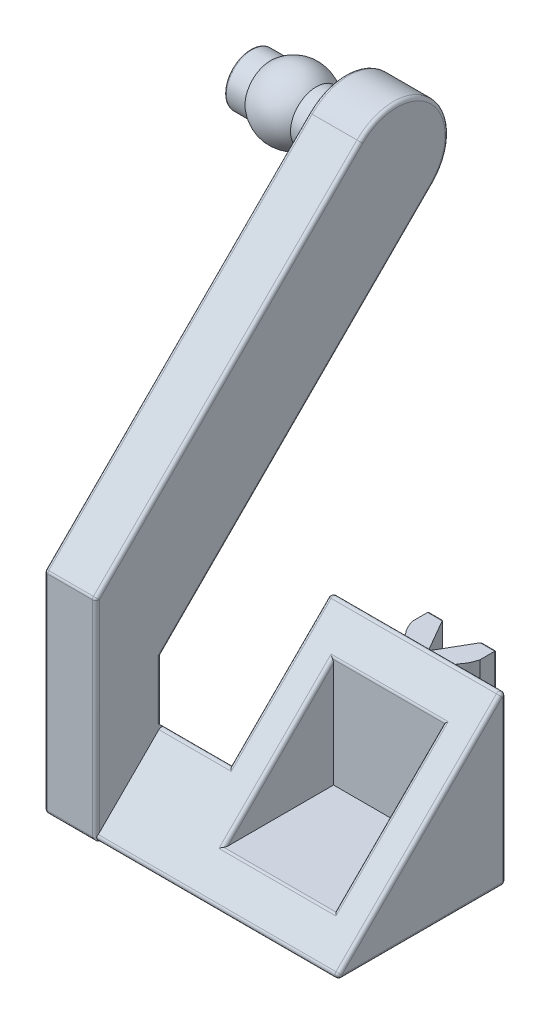
SolidWorks part; units mm, degrees
ref_plane "前视基准面" through (0, 0, 0) normal (0, 0, 1) x (1, 0, 0)
ref_plane "上视基准面" through (0, 0, 0) normal (0, 1, 0) x (1, 0, 0)
ref_plane "右视基准面" through (0, 0, 0) normal (1, 0, 0) x (0, 0, -1)
sketch "草图1" plane through (0, 0, 0) normal (1, 0, 0) x (0, 0, -1)
  line L0 (0, 0) -> (-10, 0)
  line L1 (-10, 0) -> (0, 10)
  line L2 (0, 10) -> (0, 0)
  dimension "D1" = 10
  dimension "D2" = 10
extrude "凸台-拉伸1" add sketch "草图1" along normal blind 10
sketch "草图2" plane through (0, 0, 0) normal (0, 0, 1) x (1, 0, 0)
  line L0 (0, 10) -> (0, 0) construction
  line L1 (1.8, 1.8) -> (8.2, 1.8)
  line L2 (1.8, 1.8) -> (1.8, 8.2)
  line L3 (1.8, 8.2) -> (8.2, 8.2)
  line L4 (8.2, 1.8) -> (8.2, 8.2)
  line L5 (10, 10) -> (10, 0) construction
  line L6 (10, 0) -> (0, 0) construction
  line L7 (10, 10) -> (0, 10) construction
  dimension "D1" = 1.8
  dimension "D2" = 1.8
  dimension "D3" = 1.8
  dimension "D4" = 1.8
extrude "切除-拉伸1" cut sketch "草图2" along normal up to next from offset 1.8
sketch "草图3" plane through (0, 0, 0) normal (-1, 0, 0) x (0, 0, 1)
  line L0 (10, 0) -> (2, 0)
  line L1 (10, 0) -> (0, 0) construction
  line L2 (2, 0) -> (6, 4)
  line L3 (0, 10) -> (10, 0) construction
  line L4 (6, 4) -> (10, 0)
  dimension "D1" = 90
  dimension "D2" = 8
extrude "凸台-拉伸2" add sketch "草图3" along normal blind 4
sketch "草图4" plane through (-4, 0, 0) normal (-1, 0, 0) x (0, 0, 1)
  line L0 (10, 0) -> (10, 12) construction
  line L1 (6, 4) -> (6, 7.5147)
  line L2 (9.8, 12.2) -> (-5.5563, 27.5563)
  line L3 (10, 0) -> (6, 4)
  line L4 (6, 4) -> (2, 0)
  line L5 (2, 0) -> (10, 0)
  line L6 (6, 7.5147) -> (-9.799, 23.3137)
  line L7 (6, 4) -> (2, 0)
  line L8 (2, 0) -> (9.8, 0)
  line L9 (5.7574, 7.7574) -> (-9.799, 23.3137) construction
  line L10 (9.8, 0) -> (9.8, 12.2)
  line L11 (9.8, 0) -> (9.8, 12) construction
  line L12 (9.8, 12.2) -> (10, 12) construction
  line L13 (10, 12) -> (-5.5563, 27.5563) construction
  line L14 (9.8, 0) -> (10, 0) construction
  arc A0 (-5.5563, 27.5563) -> (-9.799, 23.3137) centre (-7.6777, 25.435) ccw
  dimension "D6" = 6
  dimension "D2" = 12
  dimension "D3" = 22
  dimension "D4" = 135
  dimension "D1" = 0
  dimension "D5" = 6
  dimension "D7" = 0.2
extrude "凸台-拉伸3" add sketch "草图4" along normal blind 3
sketch "草图5" plane through (-7, 0, 0) normal (-1, 0, 0) x (0, 0, 1)
  circle A0 centre (-7.6777, 25.435) radius 1.5
  dimension "D1" = 3
extrude "凸台-拉伸4" add sketch "草图5" along normal blind 5.5
ref_plane "基准面1" through (-10, 0, 0) normal (-1, 0, 0) x (0, 0, 1)
sketch "草图6" plane through (-10, 0, 0) normal (-1, 0, 0) x (0, 0, 1)
  line L0 (-7.6777, 27.435) -> (-7.6777, 23.435)
  arc A0 (-7.6777, 23.435) -> (-7.6777, 27.435) centre (-7.6777, 25.435) ccw
  dimension "D1" = 4
revolve "旋转1" add sketch "草图6" angle 360 about L0
sketch "草图7" plane through (0, 0, 0) normal (0, -1, 0) x (1, 0, 0)
  line L0 (5, 0) -> (5, -2) construction
  line L1 (10, 0) -> (0, 0) construction
  line L2 (5, -2) -> (5, -2.5) construction
  line L3 (6.5, 0) -> (3.5, 0)
  line L4 (3.5, 0) -> (3.5, -0.6771)
  line L5 (3.8453, -2.5) -> (3.05, -2.5)
  line L6 (3.05, -2.5) -> (3.05, -1.5556)
  line L7 (5, 0) -> (5, -0.5) construction
  line L8 (5, -0.5) -> (3.8453, -2.5)
  line L9 (3.8453, -2.5) -> (5, -2.5) construction
  line L10 (5, -0.5) -> (6.1547, -2.5)
  line L11 (6.1547, -2.5) -> (6.95, -2.5)
  line L12 (6.95, -2.5) -> (6.95, -1.5556)
  line L13 (6.5, 0) -> (6.5, -0.6771)
  arc A0 (3.5, -0.6771) -> (3.05, -1.5556) centre (5, -2) ccw
  arc A1 (6.5, -0.6771) -> (6.95, -1.5556) centre (5, -2) cw
  dimension "D5" = 2
  dimension "D1" = 2
  dimension "D2" = 0.5
  dimension "D3" = 1.5
  dimension "D4" = 1.95
  dimension "D6" = 0.5
  dimension "D7" = 30
extrude "凸台-拉伸5" add sketch "草图7" against normal blind 8 from offset 1 offset against normal yes
sketch "草图8" plane through (0, 0, 0) normal (0, -1, 0) x (1, 0, 0)
  line L0 (5, -0.5) -> (3.8453, -2.5)
  line L1 (3.8453, -2.5) -> (6.1547, -2.5)
  line L2 (6.1547, -2.5) -> (5, -0.5)
extrude "凸台-拉伸6" add sketch "草图8" against normal blind 1 from offset 4.5 offset against normal yes
fillet "圆角1" radius 0.1 12 edges at (6.95, 5, -2.5) (6.5524, 9, -2.5) (6.1547, 7.25, -2.5) (5, 5.5, -2.5) (3.8453, 7.25, -2.5) (3.4476, 9, -2.5) (3.05, 5, -2.5) (3.4476, 1, -2.5) (3.8453, 2.75, -2.5) (5, 4.5, -2.5) (6.1547, 2.75, -2.5) (6.5524, 1, -2.5)
fillet "圆角3" radius 0.2 15 edges at (10, 0, 5) (10, 5, 5) (10, 5, 0) (5, 8.2, 1.8) (8.2, 5, 5) (5, 1.8, 8.2) (1.8, 5, 5) (-7, 0, 5.9) (-7, 2, 4) (0, 5, 0) (5, 0, 0)
fillet "圆角7" radius 0.2 2 edges at (9.9414, 0.0586, 9.8586) (2.9, 0, 10)
fillet "圆角8" radius 0.2 12 edges at (-7, 6.2, 9.8) (-6.9414, 0.0586, 9.8) (-4, 6.1, 9.8) (-4, 15.4142, -1.8995) (-4, 27.5563, -9.799) (-7, 15.4142, -1.8995) (-7, 27.5563, -9.799) (-4, 19.8782, 2.1218) (-7, 19.8782, 2.1218) (-4, 5.7574, 6) (-7, 5.6159, 6)
fillet "圆角9" radius 0.2 6 edges at (-6.9414, 12.1757, 9.7414) (-4.0586, 12.1757, 9.7414) (-5.5, 12.2, 9.8) (9.9414, 9.8586, 0.0586) (0.0586, 9.8586, 0.0586) (5, 10, 0)
fillet "圆角10" radius 0.1 1 edges at (-12.5, 25.435, -6.1777)
